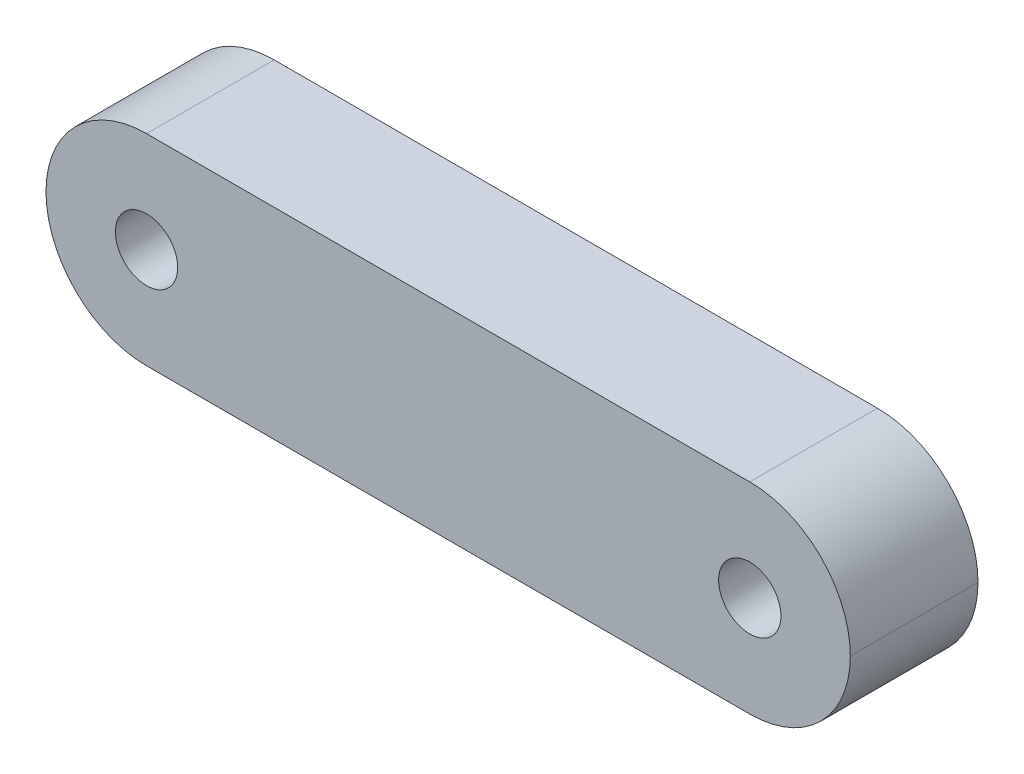
SolidWorks part; units mm, degrees
ref_plane "Front Plane" through (0, 0, 0) normal (0, 0, 1) x (1, 0, 0)
ref_plane "Top Plane" through (0, 0, 0) normal (0, 1, 0) x (1, 0, 0)
ref_plane "Right Plane" through (0, 0, 0) normal (1, 0, 0) x (0, 0, -1)
sketch "Sketch1" plane through (0, 0, 0) normal (0, 0, 1) x (1, 0, 0)
  line L1 (0, 0) -> (40, 0)
  line L2 (0, 0) -> (0, 10)
  line L3 (0, 10) -> (40, 10)
  line L4 (40, 0) -> (40, 10)
  circle A1 centre (35, 5) radius 1.55
  circle A2 centre (5, 5) radius 1.55
  dimension "D3" = 5
  dimension "D4" = 3.1
  dimension "D5" = 5
  dimension "D6" = 3.1
  dimension "D1" = 10
  dimension "D2" = 40
extrude "Boss-Extrude1" add sketch "Sketch1" along normal blind 6.35 contours L1 L4 L3 L2 A2 A1 | A2 region at (20, 5, 0)
fillet "Fillet1" radius 5 4 edges at (0, 10, 3.175) (0, 0, 3.175) (40, 10, 3.175) (40, 0, 3.175)
